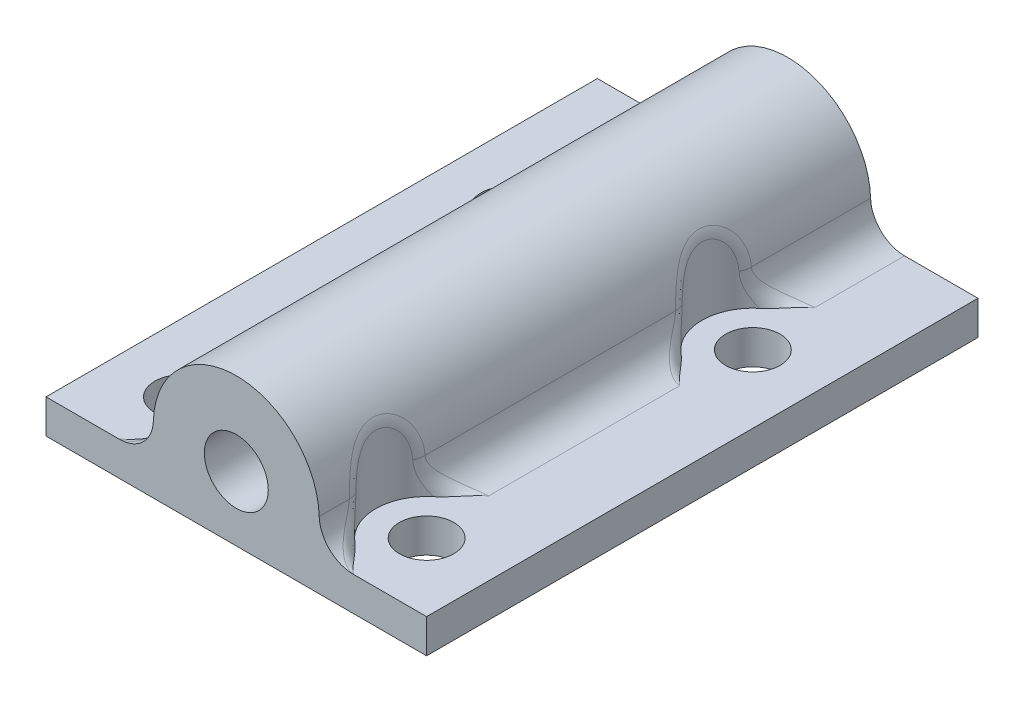
SolidWorks part; units mm, degrees
ref_plane "Front Plane" through (0, 0, 0) normal (0, 0, 1) x (1, 0, 0)
ref_plane "Top Plane" through (0, 0, 0) normal (0, 1, 0) x (1, 0, 0)
ref_plane "Right Plane" through (0, 0, 0) normal (1, 0, 0) x (0, 0, -1)
sketch "Sketch1" plane through (0, 0, 0) normal (0, 1, 0) x (1, 0, 0)
  line L0 (0, 13.6) -> (0, 0) construction
  line L1 (-11.2, 13.6) -> (11.2, 13.6)
  line L2 (-11.2, 13.6) -> (-11.2, -13.6)
  line L3 (-11.2, -13.6) -> (11.2, -13.6)
  line L4 (11.2, 13.6) -> (11.2, -13.6)
  line L5 (0, 0) -> (11.2, 0) construction
  line L6 (11.2, -13.6) -> (11.2, 13.6) construction
  line L7 (11.2, 13.6) -> (-11.2, 13.6) construction
  circle A0 centre (7.2, -9.6) radius 1.6
  circle A1 centre (-7.2, -9.6) radius 1.6
  circle A2 centre (-7.2, 9.6) radius 1.6
  circle A3 centre (7.2, 9.6) radius 1.6
  circle A4 centre (7.2, -9.6) radius 1.6 construction
  circle A5 centre (-7.2, -9.6) radius 1.6 construction
  circle A6 centre (-7.2, 9.6) radius 1.6 construction
  circle A7 centre (7.2, 9.6) radius 1.6 construction
sketch "Sketch3" plane through (0, 0, 0) normal (0, 1, 0) x (1, 0, 0)
  line L0 (-3.7, -6.7) -> (-3.7, 6.7)
  line L1 (3.2, -6.2) -> (-3.2, -6.2) construction
  line L2 (3.2, -6.2) -> (3.2, 6.2) construction
  line L3 (3.2, 6.2) -> (-3.2, 6.2) construction
  line L4 (-3.2, -6.2) -> (-3.2, 6.2) construction
  line L5 (3.7, 6.7) -> (-3.7, 6.7)
  line L6 (3.7, -6.7) -> (3.7, 6.7)
  line L7 (3.7, -6.7) -> (-3.7, -6.7)
  line L8 (3.7, 6.7) -> (3.7, 16.85) construction
  line L9 (3.7, 16.85) -> (-3.7, 16.85) construction
  line L10 (-3.7, 16.85) -> (-3.7, 6.7) construction
  line L11 (-11.2, 18.85) -> (11.2, 18.85) construction
  line L12 (3.7, 3.8) -> (-3.7, 3.8) construction
  line L13 (-3.2, 3.8) -> (-0.2, 3.8) construction
  line L14 (3.7, -2.85) -> (-3.7, -2.85) construction
  line L15 (-2.25, -2.35) -> (2.25, -2.35) construction
  line L16 (2.25, -2.85) -> (2.25, 3.8) construction
  line L17 (11.2, 18.85) -> (11.2, -13.6) construction
  line L18 (-11.2, -13.6) -> (-11.2, 18.85) construction
  line L19 (-11.2, -13.6) -> (11.2, -13.6) construction
  line L20 (11.2, 13.6) -> (11.2, -13.6) construction
  line L21 (3.7, 9.7) -> (-3.7, 9.7) construction
  line L22 (-2.25, 9.7) -> (-2.25, -2.85) construction
  line L23 (-2.25, 16.85) -> (-2.25, 16.35) construction
  line L24 (-2.25, 16.35) -> (-2.25, 9.7) construction
  dimension "D2" = 2
  dimension "D3" = 10.15
  dimension "D4" = 13.05
  dimension "D5" = 0.5
  dimension "D6" = 6.65
  dimension "D7" = 3
  dimension "D8" = 12.55
  dimension "D9" = 0.5
  dimension "D1" = 0.5
sketch "Sketch4" plane through (0, 0, 0) normal (0, 0, 1) x (1, 0, 0)
  line L0 (2.25, 2.5) -> (-2.25, 2.5) construction
  line L1 (2.25, 2.5) -> (2.25, 0) construction
  line L2 (0, 0) -> (0, 3.7987) construction
  line L4 (0, 0) -> (-11.2, 0) construction
  line L5 (-2.25, 0) -> (-2.25, 2.5) construction
  line L6 (2.7026, 2.8) -> (-2.7026, 2.8) construction
  line L12 (11.2, 0) -> (11.2, 2)
  line L13 (11.2, 2) -> (-11.2, 2) construction
  line L14 (-11.2, 2) -> (-11.2, 0)
  line L15 (11.2, 0) -> (-11.2, 0)
  line L16 (11.2, 2) -> (6.8783, 2)
  line L17 (-6.8783, 2) -> (-11.2, 2)
  line L19 (3.7, 0) -> (-3.7, 0) construction
  line L21 (3.7, 0) -> (2.7375, 2.0239) construction
  line L22 (-3.7, 0) -> (-2.7375, 2.0239) construction
  circle A0 centre (0, 3.7987) radius 2.8813 construction
  circle A1 centre (0, 3.7987) radius 2.8813 construction
  arc A2 (2.7026, 2.8) -> (2.7375, 2.0239) centre (3.6406, 2.4534) ccw construction
  arc A3 (-2.7026, 2.8) -> (-2.7375, 2.0239) centre (-3.6406, 2.4534) cw construction
  arc A4 (2.7375, 2.0239) -> (-2.7375, 2.0239) centre (0, 0.7221) ccw construction
  circle A5 centre (0, 3.7987) radius 4.8813 construction
  arc A6 (4.8792, 3.9415) -> (6.8783, 2) centre (6.8783, 4) ccw
  arc A7 (-6.8783, 2) -> (-4.8792, 3.9415) centre (-6.8783, 4) ccw
  arc A8 (4.8792, 3.9415) -> (-4.8792, 3.9415) centre (0, 3.7987) ccw
  dimension "D2" = 1
  dimension "D4" = 2
  dimension "D5" = 2
  dimension "D1" = 0.3
  dimension "D3" = 2
extrude "Boss-Extrude1" add sketch "Sketch4" against normal up to vertex (18.85 mm away) from vertex up to point (11.2, 0, -18.85) starting at point (11.2, 0, 13.6)
sketch "Sketch5" plane through (0, 0, 0) normal (0, 1, 0) x (1, 0, 0)
  circle A0 centre (7.2, 9.6) radius 1.6 construction
  circle A1 centre (7.2, -9.6) radius 1.6 construction
  circle A2 centre (-7.2, -9.6) radius 1.6 construction
  circle A3 centre (-7.2, 9.6) radius 1.6 construction
  circle A4 centre (7.2, 9.6) radius 1.6
  circle A5 centre (7.2, -9.6) radius 1.6
  circle A6 centre (-7.2, -9.6) radius 1.6
  circle A7 centre (-7.2, 9.6) radius 1.6
extrude "Cut-Extrude1" cut sketch "Sketch5" along normal through all
sketch "Sketch6" plane through (0, 2, 0) normal (0, 1, 0) x (1, 0, 0)
  circle A0 centre (-7.2, 9.6) radius 1.6 construction
  circle A1 centre (-7.2, -9.6) radius 1.6 construction
  circle A2 centre (7.2, 9.6) radius 1.6 construction
  circle A3 centre (7.2, -9.6) radius 1.6 construction
  circle A4 centre (-7.2, 9.6) radius 1.6 construction
  circle A5 centre (-7.2, -9.6) radius 1.6 construction
  circle A6 centre (7.2, 9.6) radius 1.6 construction
  circle A7 centre (7.2, -9.6) radius 1.6 construction
  circle A8 centre (7.2, -9.6) radius 3
  circle A9 centre (7.2, 9.6) radius 3
  circle A10 centre (-7.2, 9.6) radius 3
  circle A11 centre (-7.2, -9.6) radius 3
  dimension "D1" = 6
extrude "Cut-Extrude2" cut sketch "Sketch6" along normal through all
fillet "Fillet1" radius 1 12 edges at (-5.1994, 2.9132, 11.8355) (-4.2008, 6.2847, 9.5328) (-5.1994, 2.9132, -7.3645) (-4.2008, 6.2847, -9.6672) (5.7696, 2.3354, -6.9629) (4.2008, 6.2847, -9.5328) (5.7696, 2.3354, 12.2371) (5.0589, 3.1695, 7.4986) (-8.0354, 5.6313, 6.7187) (-8.0354, 5.6313, -12.4813) (5.0589, 3.1695, -11.7014) (4.2008, 6.2847, 9.6672)
sketch "Sketch7" plane through (0, 0, 0) normal (0, 0, 1) x (1, 0, 0)
  circle A0 centre (0, 3.7987) radius 2.8813 construction
  circle A1 centre (0, 3.7987) radius 2.8813
extrude "Cut-Extrude3" cut sketch "Sketch7" against normal up to vertex (16.85 mm away) from vertex up to point (3.7, 0, -16.85) starting at point (3.7, 0, 2.85)
sketch "Sketch9" plane through (0, 0, 0) normal (0, 0, 1) x (1, 0, 0)
  line L0 (3.7, 0) -> (2.7375, 2.0239) construction
  line L1 (-3.7, 0) -> (-2.7375, 2.0239) construction
  line L2 (3.7, 0) -> (2.7375, 2.0239)
  line L3 (-3.7, 0) -> (-2.7375, 2.0239)
  line L4 (3.7, 0) -> (-3.7, 0)
  arc A0 (2.7375, 2.0239) -> (-2.7375, 2.0239) centre (0, 0.7221) ccw construction
  arc A1 (2.7375, 2.0239) -> (-2.7375, 2.0239) centre (0, 0.7221) ccw
extrude "Cut-Extrude4" cut sketch "Sketch9" against normal up to vertex (-2.85 mm away) from vertex up to point (3.7, 0, 2.85) starting at point (3.7, 0, 6.7)
sketch "Sketch10" plane through (0, 0, 0) normal (0, 0, 1) x (1, 0, 0)
  line L0 (-3.7, 0) -> (-2.7375, 2.0239) construction
  line L1 (3.7, 0) -> (2.7375, 2.0239) construction
  line L2 (-3.7, 0) -> (-2.7375, 2.0239)
  line L3 (3.7, 0) -> (2.7375, 2.0239)
  line L4 (3.7, 0) -> (-3.7, 0)
  circle A0 centre (0, 3.7987) radius 2.8813 construction
  arc A1 (2.7026, 2.8) -> (2.7375, 2.0239) centre (3.6406, 2.4534) ccw construction
  arc A2 (-2.7375, 2.0239) -> (-2.7026, 2.8) centre (-3.6406, 2.4534) ccw construction
  arc A3 (2.7026, 2.8) -> (-2.7026, 2.8) centre (0, 3.7987) ccw
  arc A4 (2.7026, 2.8) -> (2.7375, 2.0239) centre (3.6406, 2.4534) ccw
  arc A5 (-2.7375, 2.0239) -> (-2.7026, 2.8) centre (-3.6406, 2.4534) ccw
extrude "Cut-Extrude5" cut sketch "Sketch10" against normal up to vertex (6.7 mm away) from vertex up to point (3.7, 0, -6.7) starting at point (3.7, 0, 2.85)
sketch "Sketch11" plane through (0, 0, 0) normal (0, 0, 1) x (1, 0, 0)
  circle A0 centre (0, 3.7987) radius 2.3813 construction
  circle A1 centre (0, 3.7987) radius 2.3813 construction
  circle A2 centre (0, 3.7987) radius 1.8813
  dimension "D1" = 0.5
extrude "Cut-Extrude6" cut sketch "Sketch11" against normal through all and the other way through all
